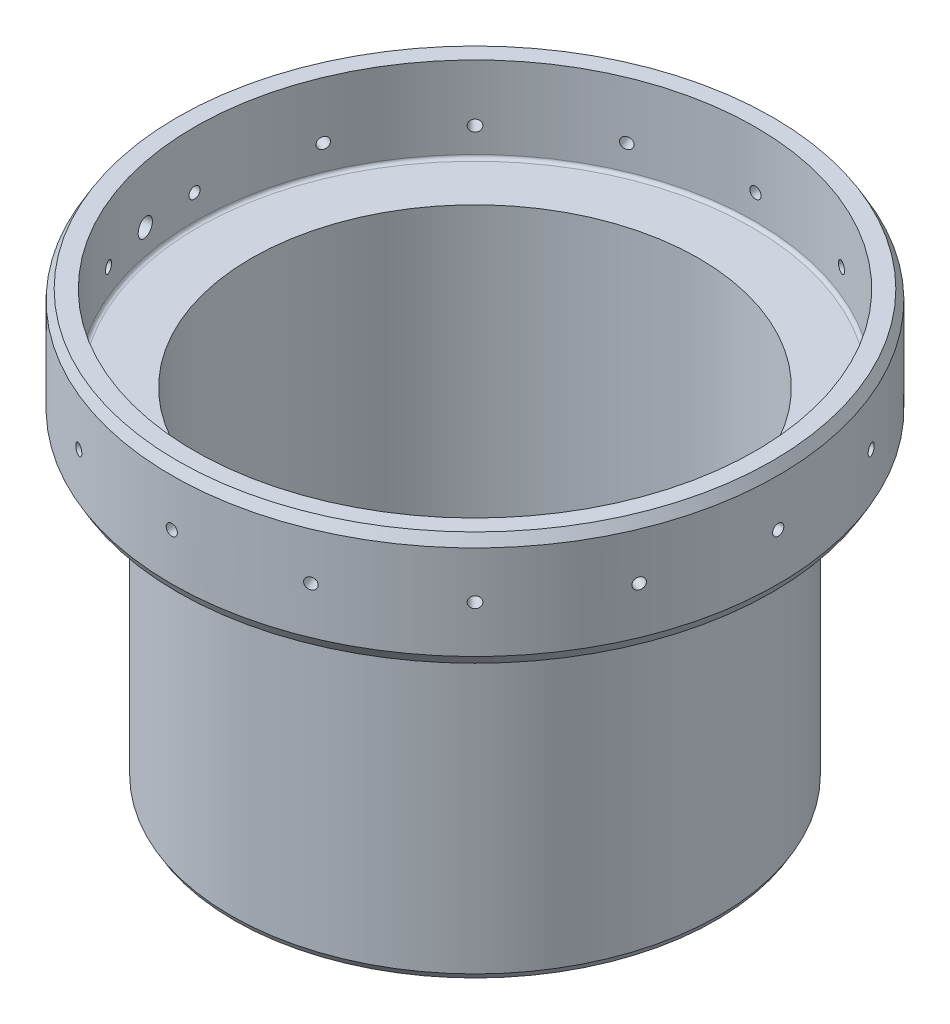
SolidWorks part; units mm, degrees
material "6061-T6 (SS)"
ref_plane "Front Plane" through (0, 0, 0) normal (0, 0, 1) x (1, 0, 0)
ref_plane "Top Plane" through (0, 0, 0) normal (0, 1, 0) x (1, 0, 0)
ref_plane "Right Plane" through (0, 0, 0) normal (1, 0, 0) x (0, 0, -1)
sketch "Sketch1" plane through (0, 0, 0) normal (0, 0, 1) x (1, 0, 0)
  line L0 (0, 0) -> (0, 9.1321) construction
  line L1 (0, 0) -> (-62.6618, 0) construction
  line L2 (-62.6618, 0) -> (-67.7418, 0)
  line L3 (-67.7418, 0) -> (-67.7418, -25.4)
  line L4 (-67.7418, -25.4) -> (-54.5528, -25.4)
  line L5 (-54.5528, -25.4) -> (-54.5528, -95.25)
  line L6 (-54.5528, -95.25) -> (-49.9808, -95.25)
  line L7 (-49.9808, -95.25) -> (-49.9808, -19.05)
  line L8 (-49.9808, -19.05) -> (-62.6618, -19.05)
  line L9 (-62.6618, -19.05) -> (-62.6618, 0)
  dimension "D1" = 5.08
  dimension "D2" = 67.7418
  dimension "D3" = 25.4
  dimension "D4" = 6.35
  dimension "D5" = 69.85
  dimension "D6" = 4.572
  dimension "D7" = 54.5528
revolve "Revolve6" add sketch "Sketch1" angle 360 about L0
sketch "Sketch2" plane through (0, 0, 0) normal (0, 1, 0) x (1, 0, 0)
  line L0 (0, 0) -> (-67.7418, 0) construction
  line L1 (0, 0) -> (-66.4402, -13.2158) construction
  circle A0 centre (0, 0) radius 67.7418 construction
  dimension "D1" = 11.25
ref_plane "Plane1" through (-67.7418, 0, 0) normal (-1, 0, 0) x (0, 0, 1)
sketch "Sketch3" plane through (-67.7418, 0, 0) normal (-1, 0, 0) x (0, 0, 1)
  line L0 (0, 0) -> (0, -12.7) construction
  dimension "D1" = 12.7
hole_wizard "Tap Drill for M3x0.5 Tap1" positions "Sketch5" profile "Sketch4" hole size "M3x0.5" standard "Ansi Metric"
sketch "Sketch5" plane through (-67.7418, 0, 0) normal (-1, 0, 0) x (0, 0, 1)
  point P1 (0, -12.7)
sketch "Sketch4" plane through (-67.7418, -12.7, 0) normal (0, 1, 0) x (0, 0, 1)
  line L0 (0, 0) -> (0, 10.9111)
  line L1 (0, 10.9111) -> (1.25, 10.16)
  line L2 (1.25, 10.16) -> (1.25, 0)
  line L5 (1.25, 0) -> (0, 0)
  line L10 (0, 10.9111) -> (-1.25, 10.16) construction
  line L11 (0, -6.35) -> (0, 107.95) construction
  dimension "Hole Dia." = 2.5
  dimension "Hole Depth" = 10.16
  dimension "Drill Angle" = 118
pattern_circular "CirPattern1" count 16 over 360 about axis through (0, 0, 0) along (0, -1, 0) of "Tap Drill for M3x0.5 Tap1"
ref_plane "Plane2" through (-66.4402, 0, 13.2158) normal (-0.9808, 0, 0.1951) x (0.1951, 0, 0.9808)
sketch "Sketch6" plane through (-66.4402, 0, 13.2158) normal (-0.9808, 0, 0.1951) x (0.1951, 0, 0.9808)
  line L0 (0, 0) -> (0, -12.7) construction
  dimension "D1" = 12.7
hole_wizard "Tap Drill for #10-32 Tap1" positions "Sketch8" profile "Sketch7" hole size "#10-32" standard "Ansi Inch"
sketch "Sketch8" plane through (-66.4402, 0, 13.2158) normal (-0.9808, 0, 0.1951) x (0.1951, 0, 0.9808)
  point P1 (0, -12.7)
sketch "Sketch7" plane through (-66.4402, -12.7, 13.2158) normal (0, 1, 0) x (0.1951, 0, 0.9808)
  line L0 (0, 0) -> (0, 11.3733)
  line L1 (0, 11.3733) -> (2.0193, 10.16)
  line L2 (2.0193, 10.16) -> (2.0193, 0)
  line L5 (2.0193, 0) -> (0, 0)
  line L10 (0, 11.3733) -> (-2.0193, 10.16) construction
  line L11 (0, -6.35) -> (0, 107.95) construction
  dimension "Hole Dia." = 4.0386
  dimension "Hole Depth" = 10.16
  dimension "Drill Angle" = 118
sketch "Sketch9" plane through (0, -95.25, 0) normal (0, -1, 0) x (1, 0, 0)
  line L0 (54.5528, 0) -> (49.9808, 0) construction
  circle A1 centre (0, 0) radius 54.5528 construction
  circle A2 centre (0, 0) radius 49.9808 construction
  point P9 (52.2668, 0)
  dimension "D1" = 52.2668
hole_wizard "Tap Drill for #4-40 Tap1" positions "3DSketch1" profile "Sketch10" hole size "#4-40" standard "Ansi Inch"
sketch3d "3DSketch1"
  point P0 (52.2668, -95.25, 0)
sketch "Sketch10" plane through (52.2668, -95.25, 0) normal (1, 0, 0) x (0, 0, -1)
  line L0 (0, 0) -> (0, 18.4592)
  line L1 (0, 18.4592) -> (1.1303, 17.78)
  line L2 (1.1303, 17.78) -> (1.1303, 0)
  line L5 (1.1303, 0) -> (0, 0)
  line L10 (0, 18.4592) -> (-1.1303, 17.78) construction
  line L11 (0, -6.35) -> (0, 107.95) construction
  dimension "Hole Dia." = 2.2606
  dimension "Hole Depth" = 17.78
  dimension "Drill Angle" = 118
pattern_circular "CirPattern2" count 16 over 360 about axis through (0, 0, 0) along (0, -1, 0) of "Tap Drill for #4-40 Tap1"
chamfer "Chamfer2" distance 1.27 angle 60 2 edges at (0, -25.4, -67.7418) (0, 0, -67.7418) first distance on face at (0, -25.4, -54.5528) first distance on face at (0, 0, -67.7418)
chamfer "Chamfer4" distance 0.762 angle 60 1 edges at (0, -95.25, -54.5528) first distance on face at (36.9582, -95.25, -38.0885)
chamfer "Chamfer5" distance 0.762 angle 60 1 edges at (0, -95.25, -49.9808) first distance on face at (0, -95.25, 53.7908)
fillet "Fillet1" radius 0.762 2 edges at (0, -25.4, -54.5528) (0, -19.05, -62.6618)
